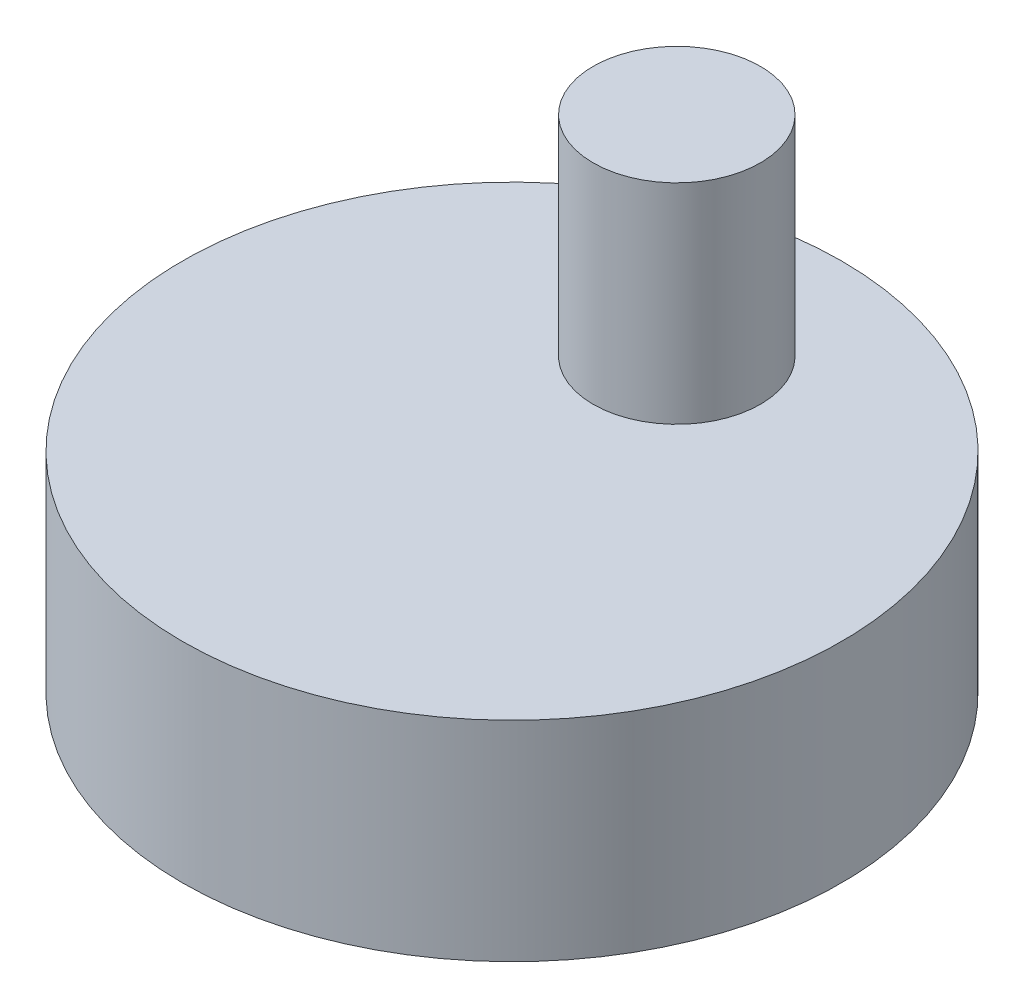
SolidWorks part; units mm, degrees
ref_plane "Front Plane" through (0, 0, 0) normal (0, 0, 1) x (1, 0, 0)
ref_plane "Top Plane" through (0, 0, 0) normal (0, 1, 0) x (1, 0, 0)
ref_plane "Right Plane" through (0, 0, 0) normal (1, 0, 0) x (0, 0, -1)
sketch "Sketch1" plane through (0, 0, 0) normal (0, 1, 0) x (1, 0, 0)
  circle A0 centre (0, 0) radius 7.88
  circle A1 centre (0, 3.94) radius 2
  dimension "D1" = 15.76
  dimension "D2" = 4
  dimension "D3" = 3.94
extrude "Boss-Extrude1" add sketch "Sketch1" along normal blind 5 contours A0
extrude "Boss-Extrude2" add sketch "Sketch1<3>" along normal blind 10 contours A1
sketch "Sketch1<3>" plane through (0, 0, 0) normal (0, 1, 0) x (1, 0, 0) same geometry as "Sketch1"
